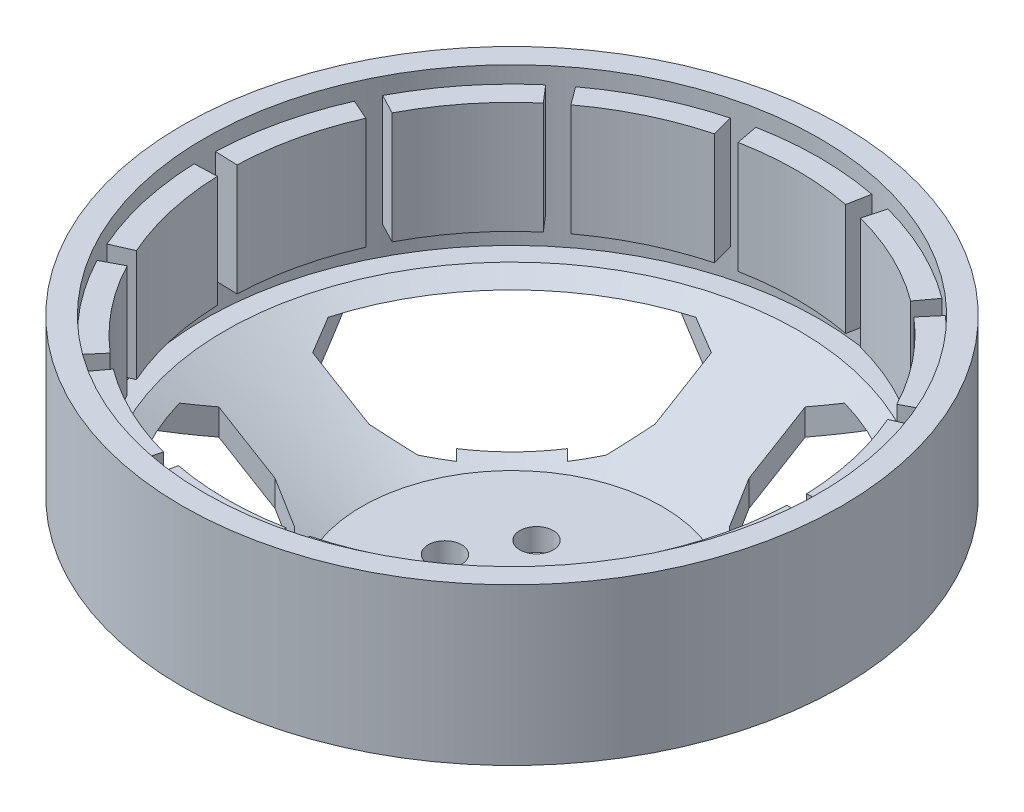
SolidWorks part; units mm, degrees
ref_plane "Ön Düzlem" through (0, 0, 0) normal (0, 0, 1) x (1, 0, 0)
ref_plane "Üst Düzlem" through (0, 0, 0) normal (0, 1, 0) x (1, 0, 0)
ref_plane "Sağ Düzlem" through (0, 0, 0) normal (1, 0, 0) x (0, 0, -1)
sketch "Çizim1" plane through (0, 0, 0) normal (0, 1, 0) x (1, 0, 0)
  circle A0 centre (0, 0) radius 29.5
  circle A1 centre (0, 0) radius 27.5
  dimension "D1" = 59
  dimension "D2" = 2
extrude "Yükseklik-Ekstrüzyon1" add sketch "Çizim1" along normal blind 12
sketch "Çizim2" plane through (0, 0, 0) normal (0, 1, 0) x (1, 0, 0)
  line L0 (6.5305, 24.6496) -> (7.0427, 26.5829)
  line L1 (-4.8113, 25.042) -> (-5.1887, 27.0061)
  line L2 (4.8113, 25.042) -> (5.1887, 27.0061)
  line L3 (15.2002, 20.4745) -> (16.3923, 22.0803)
  line L4 (16.5788, 19.3751) -> (17.8791, 20.8947)
  line L5 (22.5784, 11.8518) -> (24.3493, 12.7813)
  line L6 (23.3435, 10.2631) -> (25.1744, 11.068)
  line L7 (25.4848, 0.8817) -> (27.4836, 0.9508)
  line L8 (25.4848, -0.8817) -> (27.4836, -0.9508)
  line L9 (23.3435, -10.2631) -> (25.1744, -11.068)
  line L10 (22.5784, -11.8518) -> (24.3493, -12.7813)
  line L11 (16.5788, -19.3751) -> (17.8791, -20.8947)
  line L12 (15.2002, -20.4745) -> (16.3923, -22.0803)
  line L13 (6.5305, -24.6496) -> (7.0427, -26.5829)
  line L14 (4.8113, -25.042) -> (5.1887, -27.0061)
  line L15 (-4.8113, -25.042) -> (-5.1887, -27.0061)
  line L16 (-6.5305, -24.6496) -> (-7.0427, -26.5829)
  line L17 (-15.2002, -20.4745) -> (-16.3923, -22.0803)
  line L18 (-16.5788, -19.3751) -> (-17.8791, -20.8947)
  line L19 (-22.5784, -11.8518) -> (-24.3493, -12.7813)
  line L20 (-23.3435, -10.2631) -> (-25.1744, -11.068)
  line L21 (-25.4848, -0.8817) -> (-27.4836, -0.9508)
  line L22 (-25.4848, 0.8817) -> (-27.4836, 0.9508)
  line L23 (-23.3435, 10.2631) -> (-25.1744, 11.068)
  line L24 (-22.5784, 11.8518) -> (-24.3493, 12.7813)
  line L25 (-16.5788, 19.3751) -> (-17.8791, 20.8947)
  line L26 (-15.2002, 20.4745) -> (-16.3923, 22.0803)
  line L27 (-6.5305, 24.6496) -> (-7.0427, 26.5829)
  arc A0 (4.8113, 25.042) -> (-4.8113, 25.042) centre (0, 0) ccw
  circle A2 centre (0, 0) radius 27.5 construction
  arc A3 (15.2002, 20.4745) -> (6.5305, 24.6496) centre (0, 0) ccw
  arc A4 (22.5784, 11.8518) -> (16.5788, 19.3751) centre (0, 0) ccw
  arc A5 (25.4848, 0.8817) -> (23.3435, 10.2631) centre (0, 0) ccw
  arc A6 (23.3435, -10.2631) -> (25.4848, -0.8817) centre (0, 0) ccw
  arc A7 (16.5788, -19.3751) -> (22.5784, -11.8518) centre (0, 0) ccw
  arc A8 (6.5305, -24.6496) -> (15.2002, -20.4745) centre (0, 0) ccw
  arc A9 (-4.8113, -25.042) -> (4.8113, -25.042) centre (0, 0) ccw
  arc A10 (-15.2002, -20.4745) -> (-6.5305, -24.6496) centre (0, 0) ccw
  arc A11 (-22.5784, -11.8518) -> (-16.5788, -19.3751) centre (0, 0) ccw
  arc A12 (-25.4848, -0.8817) -> (-23.3435, -10.2631) centre (0, 0) ccw
  arc A13 (-23.3435, 10.2631) -> (-25.4848, 0.8817) centre (0, 0) ccw
  arc A14 (-16.5788, 19.3751) -> (-22.5784, 11.8518) centre (0, 0) ccw
  arc A15 (-6.5305, 24.6496) -> (-15.2002, 20.4745) centre (0, 0) ccw
  arc A16 (-25.1744, 11.068) -> (-27.4836, 0.9508) centre (0, 0) ccw
  arc A17 (-7.0427, 26.5829) -> (-16.3923, 22.0803) centre (0, 0) ccw
  arc A18 (-7.0427, 26.5829) -> (-16.3923, 22.0803) centre (0, 0) ccw
  arc A19 (-17.8791, 20.8947) -> (-24.3493, 12.7813) centre (0, 0) ccw
  arc A20 (-17.8791, 20.8947) -> (-24.3493, 12.7813) centre (0, 0) ccw
  arc A21 (-25.1744, 11.068) -> (-27.4836, 0.9508) centre (0, 0) ccw
  arc A22 (-27.4836, -0.9508) -> (-25.1744, -11.068) centre (0, 0) ccw
  arc A23 (-27.4836, -0.9508) -> (-25.1744, -11.068) centre (0, 0) ccw
  arc A24 (-24.3493, -12.7813) -> (-17.8791, -20.8947) centre (0, 0) ccw
  arc A25 (-24.3493, -12.7813) -> (-17.8791, -20.8947) centre (0, 0) ccw
  arc A26 (-16.3923, -22.0803) -> (-7.0427, -26.5829) centre (0, 0) ccw
  arc A27 (-16.3923, -22.0803) -> (-7.0427, -26.5829) centre (0, 0) ccw
  arc A28 (-5.1887, -27.0061) -> (5.1887, -27.0061) centre (0, 0) ccw
  arc A29 (-5.1887, -27.0061) -> (5.1887, -27.0061) centre (0, 0) ccw
  arc A30 (7.0427, -26.5829) -> (16.3923, -22.0803) centre (0, 0) ccw
  arc A31 (7.0427, -26.5829) -> (16.3923, -22.0803) centre (0, 0) ccw
  arc A32 (17.8791, -20.8947) -> (24.3493, -12.7813) centre (0, 0) ccw
  arc A33 (17.8791, -20.8947) -> (24.3493, -12.7813) centre (0, 0) ccw
  arc A34 (25.1744, -11.068) -> (27.4836, -0.9508) centre (0, 0) ccw
  arc A35 (25.1744, -11.068) -> (27.4836, -0.9508) centre (0, 0) ccw
  arc A36 (27.4836, 0.9508) -> (25.1744, 11.068) centre (0, 0) ccw
  arc A37 (27.4836, 0.9508) -> (25.1744, 11.068) centre (0, 0) ccw
  arc A38 (24.3493, 12.7813) -> (17.8791, 20.8947) centre (0, 0) ccw
  arc A39 (24.3493, 12.7813) -> (17.8791, 20.8947) centre (0, 0) ccw
  arc A40 (16.3923, 22.0803) -> (7.0427, 26.5829) centre (0, 0) ccw
  arc A41 (16.3923, 22.0803) -> (7.0427, 26.5829) centre (0, 0) ccw
  arc A42 (5.1887, 27.0061) -> (-5.1887, 27.0061) centre (0, 0) ccw
  arc A43 (5.1887, 27.0061) -> (-5.1887, 27.0061) centre (0, 0) ccw
  point P65 (0, 0)
  dimension "D1" = 2
  dimension "D2" = 14
extrude "Yükseklik-Ekstrüzyon3" add sketch "Çizim2" along normal blind 10 from offset 0.5 contours L2 A42 L1 A0 | L27 A17 L26 A15 | L25 A19 L24 A14 | L23 A16 L22 A13 | L21 A22 L20 A12 | L19 A24 L18 A11 | L17 A26 L16 A10 | L15 A28 L14 A9 | L13 A30 L12 A8 | L11 A32 L10 A7 | L9 A34 L8 A6 | L7 A36 L6 A5 | L5 A38 L4 A4 | L3 A40 L0 A3 region at (11.4344, 0, -23.7438) region at (0, 0, -26.3537) region at (20.6041, 0, -16.4312) region at (25.6929, 0, -5.8642) region at (25.6929, 0, 5.8642) region at (20.6041, 0, 16.4312) region at (11.4344, 0, 23.7438) region at (0, 0, 26.3537) region at (-11.4344, 0, 23.7438) region at (-20.6041, 0, 16.4312) region at (-25.6929, 0, 5.8642) region at (-25.6929, 0, -5.8642) region at (-20.6041, 0, -16.4312) region at (-11.4344, 0, -23.7438)
sketch "Çizim3" plane through (0, 0, 0) normal (0, -1, 0) x (1, 0, 0)
  circle A0 centre (0, 0) radius 29.5
  circle A1 centre (0, 0) radius 27.5
extrude "Yükseklik-Ekstrüzyon4" add sketch "Çizim3" along normal blind 2
sketch3d "3B Çizim3"
  line L0 (0, -2, 0) -> (29.5, -2, 0)
  line L1 (0, -2, 0) -> (0, -11.5, 0)
  line L2 (0, -11.5, 0) -> (14, -11.5, 0)
  line L3 (14, -11.5, 0) -> (29.5, -2, 0)
  line L4 (0, 12, 0) -> (0, -2, 0) construction
  circle A1 centre (0, -2, 0) radius 29.5 construction
  point P7 (0, -31.5, 0)
  dimension "D1" = 9.5
  dimension "D2" = 14
ref_plane "Düzlem1" through (0, 0, 0) normal (0, 0, -1) x (-1, 0, 0)
sketch "Çizim6" plane through (0, 0, 0) normal (0, 0, -1) x (-1, 0, 0)
  line L0 (-29.5, -2) -> (0, -2)
  line L1 (0, -2) -> (0, -11.5)
  line L2 (0, -11.5) -> (-14, -11.5)
  line L3 (-14, -11.5) -> (-29.5, -2)
  line L4 (0, -2) -> (0, -43.9758) construction
  line L5 (0, -9.5) -> (-13.4359, -9.5)
  line L6 (-13.4359, -9.5) -> (-25.6727, -2)
  line L7 (-29.5, -2) -> (-25.6727, -2)
  line L8 (-13.4359, -9.5) -> (-28.4549, -0.2948) construction
  point P15 (0, 0)
  dimension "D1" = 2
revolve "Döndür1" add sketch "Çizim6" angle 360 about L4 region at (27.5864, -2.3099, 0)
sketch "Sketch2" plane through (0, -11.5, 0) normal (0, -1, 0) x (1, 0, 0)
  line L0 (0, 29.5) -> (0, -29.5) construction
  line L1 (-29.5, 0) -> (29.5, 0) construction
  line L2 (0, 24.75) -> (10, 27.7534)
  line L3 (0, 24.75) -> (0, 29.5)
  line L4 (4.2, 22.0371) -> (4.2, 17)
  line L5 (4.2, 22.0371) -> (13.6626, 26.1454)
  line L6 (4.2, 17) -> (5.5265, 13.9448)
  line L7 (0, 0) -> (20.8597, 20.8597) construction
  line L8 (17, 4.2) -> (13.9448, 5.5265)
  line L9 (22.0371, 4.2) -> (26.1454, 13.6626)
  line L10 (22.0371, 4.2) -> (17, 4.2)
  line L11 (24.75, 0) -> (29.5, 0)
  line L12 (24.75, 0) -> (27.7534, 10)
  line L13 (5.5265, 13.9448) -> (7.2608, 12.2105)
  line L14 (7.2608, 12.2105) -> (7.798, 12.7478)
  line L15 (7.798, 12.7478) -> (12.7478, 7.798)
  line L16 (13.9448, 5.5265) -> (12.2105, 7.2608)
  line L17 (12.2105, 7.2608) -> (12.7478, 7.798)
  circle A0 centre (0, 0) radius 29.5 construction
  arc A1 (0, 29.5) -> (10, 27.7534) centre (0, 0) cw
  circle A2 centre (0, 0) radius 14 construction
  arc A3 (29.5, 0) -> (27.7534, 10) centre (0, 0) ccw
  arc A4 (13.6626, 26.1454) -> (26.1454, 13.6626) centre (0, 0) cw
  point P29 (10.2729, 10.2729)
  dimension "D7" = 1
  dimension "D1" = 4.75
  dimension "D2" = 10
  dimension "D3" = 4.2
  dimension "D4" = 5
  dimension "D5" = 3
  dimension "D6" = 4
  dimension "D8" = 45
  dimension "D9" = 3.5
extrude "Cut-Extrude2" cut sketch "Sketch2" against normal blind 8.5
pattern_circular "CirPattern1" count 4 over 360 about axis through (0, -2, 0) along (0, -1, 0) of "Cut-Extrude2"
sketch "Çizim10" plane through (0, -11.5, 0) normal (0, -1, 0) x (1, 0, 0)
  line L0 (2, 0) -> (14, 0) construction
  line L1 (0, 0) -> (0, 11.7171) construction
  circle A0 centre (0, 0) radius 2
  circle A1 centre (0, 0) radius 14 construction
  circle A2 centre (6, 0) radius 1.5
  circle A3 centre (-6, 0) radius 1.5
  circle A4 centre (-3, 5.1962) radius 1.5
  circle A5 centre (3, 5.1962) radius 1.5
  circle A6 centre (6, 0) radius 1.5
  circle A7 centre (3, -5.1962) radius 1.5
  circle A8 centre (-3, -5.1962) radius 1.5
  point P12 (0, 0)
  point P13 (0, 0)
  point P14 (0, 0)
  point P25 (0, 0)
  dimension "D1" = 4
  dimension "D3" = 3
  dimension "D2" = 6
  dimension "D4" = 6
extrude "Kes-Ekstrüzyon2" cut sketch "Çizim10" against normal up to next and the other way through all contours A3 | A4 | A5 | A2 | A7 | A8 | A0
